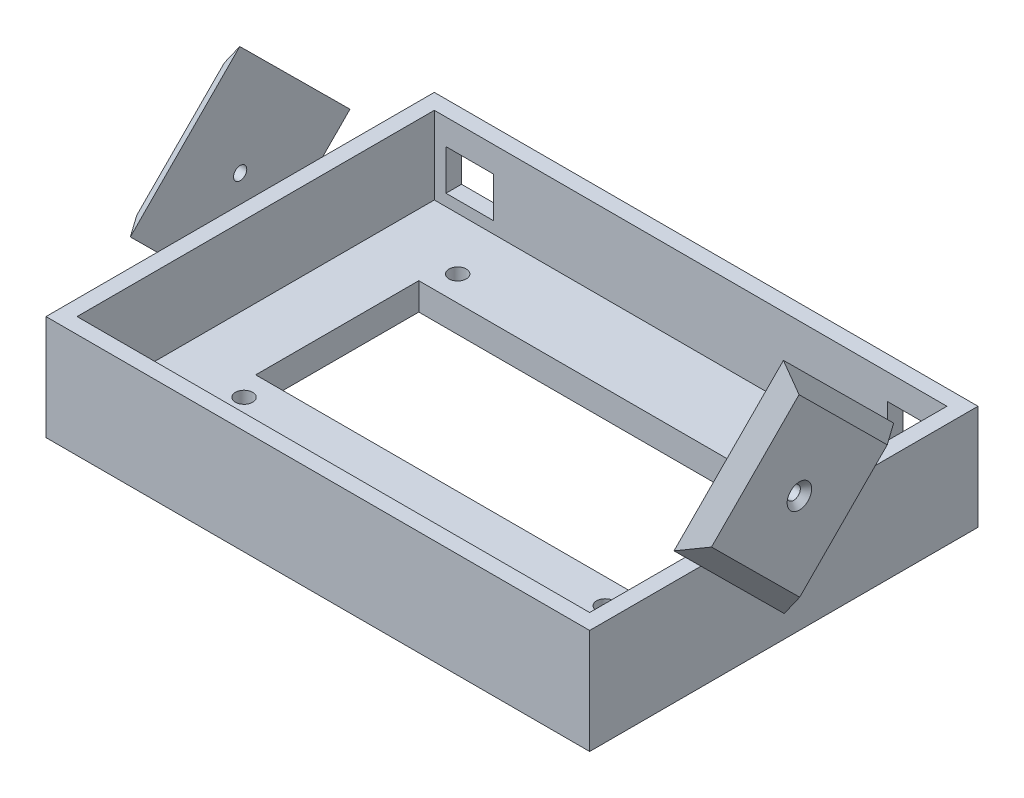
SolidWorks part; units mm, degrees
ref_plane "Спереди" through (0, 0, 0) normal (0, 0, 1) x (1, 0, 0)
ref_plane "Сверху" through (0, 0, 0) normal (0, 1, 0) x (1, 0, 0)
ref_plane "Справа" through (0, 0, 0) normal (1, 0, 0) x (0, 0, -1)
sketch "Эскиз1" plane through (0, 0, 0) normal (0, 1, 0) x (1, 0, 0)
  line L0 (0, 0) -> (140, 100) construction
  line L1 (0, 0) -> (140, 0)
  line L2 (0, 0) -> (0, 100)
  line L3 (0, 100) -> (140, 100)
  line L4 (140, 0) -> (140, 100)
  line L5 (70, 50) -> (70, 55) construction
  line L6 (70, 50) -> (70, 10) construction
  line L7 (120, 76) -> (20, 76)
  line L8 (120, 76) -> (120, 34)
  line L9 (120, 34) -> (20, 34)
  line L10 (20, 76) -> (20, 34)
  line L11 (120, 76) -> (20, 34) construction
  line L12 (120, 34) -> (20, 76) construction
  line L14 (73, 13) -> (67, 13)
  line L15 (73, 13) -> (73, 7)
  line L16 (73, 7) -> (67, 7)
  line L17 (67, 13) -> (67, 7)
  line L18 (73, 13) -> (67, 7) construction
  line L19 (73, 7) -> (67, 13) construction
  dimension "D1" = 140
  dimension "D2" = 100
  dimension "D3" = 24
  dimension "D4" = 42
  dimension "D5" = 100
  dimension "D6" = 40
  dimension "D7" = 6
extrude "Бобышка-Вытянуть1" add sketch "Эскиз1" along normal blind 7 contours L8 L7 L10 L9 | L2 L1 L4 L3 | L15 L14 L17 L16
sketch "Эскиз3" plane through (0, 7, 0) normal (0, 1, 0) x (1, 0, 0)
  line L0 (20, 34) -> (120, 76) construction
  line L1 (70, 55) -> (70, 100) construction
  line L2 (116.5, 82.5) -> (23.5, 82.5) construction
  line L3 (116.5, 82.5) -> (116.5, 27.5) construction
  line L4 (116.5, 27.5) -> (23.5, 27.5) construction
  line L5 (23.5, 82.5) -> (23.5, 27.5) construction
  line L6 (116.5, 82.5) -> (23.5, 27.5) construction
  line L7 (116.5, 27.5) -> (23.5, 82.5) construction
  line L8 (0, 100) -> (140, 100) construction
  line L9 (70, 55) -> (20, 55) construction
  line L10 (20, 76) -> (20, 34) construction
  circle A0 centre (23.5, 82.5) radius 2.225
  circle A1 centre (116.5, 82.5) radius 2.225
  circle A2 centre (116.5, 27.5) radius 2.225
  circle A3 centre (23.5, 27.5) radius 2.225
  point P4 (70, 55)
  dimension "D3" = 4.45
  dimension "D1" = 93
  dimension "D2" = 55
extrude "Вырез-Вытянуть1" cut sketch "Эскиз3" against normal blind 4
sketch "Эскиз6" plane through (0, 7, 0) normal (0, 1, 0) x (1, 0, 0)
  line L0 (73, 9.3) -> (75, 9.3) construction
  line L1 (73, 13) -> (73, 7) construction
  line L2 (73, 7) -> (67, 7) construction
  line L3 (73, 13) -> (67, 7) construction
  line L5 (72.5, 12.5) -> (67.5, 12.5) construction
  line L6 (72.5, 12.5) -> (72.5, 7.5) construction
  line L7 (72.5, 7.5) -> (67.5, 7.5) construction
  line L8 (67.5, 12.5) -> (67.5, 7.5) construction
  line L9 (72.5, 12.5) -> (67.5, 7.5) construction
  line L10 (72.5, 7.5) -> (67.5, 12.5) construction
  circle A0 centre (75, 9.3) radius 1.65
  point P11 (70, 10)
  dimension "D3" = 3.3
  dimension "D1" = 5
  dimension "D2" = 2.3
  dimension "D4" = 2.5
extrude "Вырез-Вытянуть2" cut sketch "Эскиз6" against normal blind 4 from surface starting at face at (23.5, 7, -29.725)
sketch "Эскиз7" plane through (0, 7, 0) normal (0, 1, 0) x (1, 0, 0)
  line L0 (0, 0) -> (0, 100) construction
  line L1 (4, 96) -> (136, 96)
  line L2 (4, 96) -> (4, 4)
  line L3 (4, 4) -> (136, 4)
  line L4 (136, 96) -> (136, 4)
  line L5 (140, 0) -> (140, 100) construction
  line L6 (0, 0) -> (140, 0) construction
  line L7 (0, 100) -> (140, 100) construction
  line L10 (0, 100) -> (140, 100)
  line L11 (0, 100) -> (0, 0)
  line L12 (0, 0) -> (140, 0)
  line L13 (140, 100) -> (140, 0)
  dimension "D1" = 4
  dimension "D2" = 4
  dimension "D3" = 4
  dimension "D4" = 4
extrude "Бобышка-Вытянуть2" add sketch "Эскиз7" along normal blind 20
sketch "Эскиз8" plane through (0, 0, -100) normal (0, 0, -1) x (-1, 0, 0)
  line L0 (0, 27) -> (0, 0) construction
  line L1 (-7, 10) -> (-19.3, 10)
  line L2 (-7, 10) -> (-7, 20.4)
  line L3 (-7, 20.4) -> (-19.3, 20.4)
  line L4 (-19.3, 10) -> (-19.3, 20.4)
  line L5 (0, 0) -> (-140, 0) construction
  dimension "D1" = 10.4
  dimension "D2" = 12.3
  dimension "D3" = 7
  dimension "D4" = 10
ref_plane "Плоскость1" through (70, 0, 0) normal (-1, 0, 0) x (0, 0, 1)
extrude "Вырез-Вытянуть3" cut sketch "Эскиз8" against normal up to next
mirror "Зеркальное отражение1" about plane through (70, 0, 0) normal (-1, 0, 0) of "Вырез-Вытянуть3"
sketch "Эскиз9" plane through (0, 0, 0) normal (-1, 0, 0) x (0, 0, 1)
  line L0 (-50, 0) -> (-50, 34) construction
  line L1 (0, 0) -> (-100, 0) construction
  line L2 (-100, 27) -> (0, 27) construction
  line L3 (-78.2841, 34.1057) -> (-50.1057, 5.7159)
  line L4 (-78.2841, 34.1057) -> (-49.8943, 62.2841)
  line L5 (-50.1057, 5.7159) -> (-21.7159, 33.8943)
  line L6 (-49.8943, 62.2841) -> (-21.7159, 33.8943)
  line L7 (-78.2841, 34.1057) -> (-21.7159, 33.8943) construction
  line L8 (-50.1057, 5.7159) -> (-49.8943, 62.2841) construction
  dimension "D1" = 7
  dimension "D2" = 40
extrude "Бобышка-Вытянуть3" add sketch "Эскиз9" along normal blind 4
draft "Уклон4" type of draft neutral plane draft angle 45 faces to draft 1 face at (-1.6, 21.3287, -65.6022) neutral plane through (0, 7, 0) neutral plane normal (-1, 0, 0) parameters "D1"=45
draft "Уклон5" type of draft neutral plane draft angle 45 faces to draft 1 face at (-1.6, 21.8077, -33.8932) neutral plane through (0, 7, 0) neutral plane normal (-1, 0, 0) parameters "D1"=45
draft "Уклон6" type of draft neutral plane draft angle 45 faces to draft 1 face at (-2, 48.7989, -36.5096) neutral plane through (0, 7, 0) neutral plane normal (-1, 0, 0) parameters "D1"=45
draft "Уклон7" type of draft neutral plane draft angle 45 faces to draft 1 face at (-2, 48.1949, -64.0892) neutral plane through (0, 7, 0) neutral plane normal (-1, 0, 0) parameters "D1"=45
hole_wizard "Зенковка для винта с потайной головкой M31" positions "Эскиз12" profile "Эскиз11" countersink size "M3" standard "DIN" end condition up to next
sketch "Эскиз12" plane through (-4, 0, 0) normal (-1, 0, 0) x (0, 0, 1)
  line L0 (-50.0846, 11.3727) -> (-49.9154, 56.6273) construction
  point P7 (-50, 34)
sketch "Эскиз11" plane through (-4, 34, -50) normal (0, 1, 0) x (0, 0, 1)
  line L0 (0, 0) -> (0, 4)
  line L1 (0, 4) -> (1.7, 4)
  line L2 (1.7, 4) -> (1.7, 1.45)
  line L3 (1.7, 1.45) -> (3.15, 0)
  line L5 (3.15, 0) -> (0, 0)
  line L6 (-1.7, 1.45) -> (-3.15, 0) construction
  line L11 (0, -6.35) -> (0, 107.95) construction
  dimension "Диаметр сквозного отверстия" = 3.4
  dimension "Глубина сквозного отверстия" = 4
  dimension "Диаметр передней зенковки" = 6.3
  dimension "Угол передней зенковки" = 90
mirror "Зеркальное отражение5" about plane through (70, 0, 0) normal (-1, 0, 0) of "Зенковка для винта с потайной головкой M31", "Бобышка-Вытянуть3"
draft "Уклон8" type of draft neutral plane draft angle 45 faces to draft 1 face at (141.6, 21.3287, -65.6022) neutral plane through (140, 7, 0) neutral plane normal (1, 0, 0) parameters "D1"=45
draft "Уклон9" type of draft neutral plane draft angle 45 faces to draft 3 face at (142, 48.8993, -63.3794) face at (142, 48.0892, -35.8051) face at (141.6, 21.8077, -33.8932) neutral plane through (140, 7, 0) neutral plane normal (1, 0, 0) parameters "D1"=45
